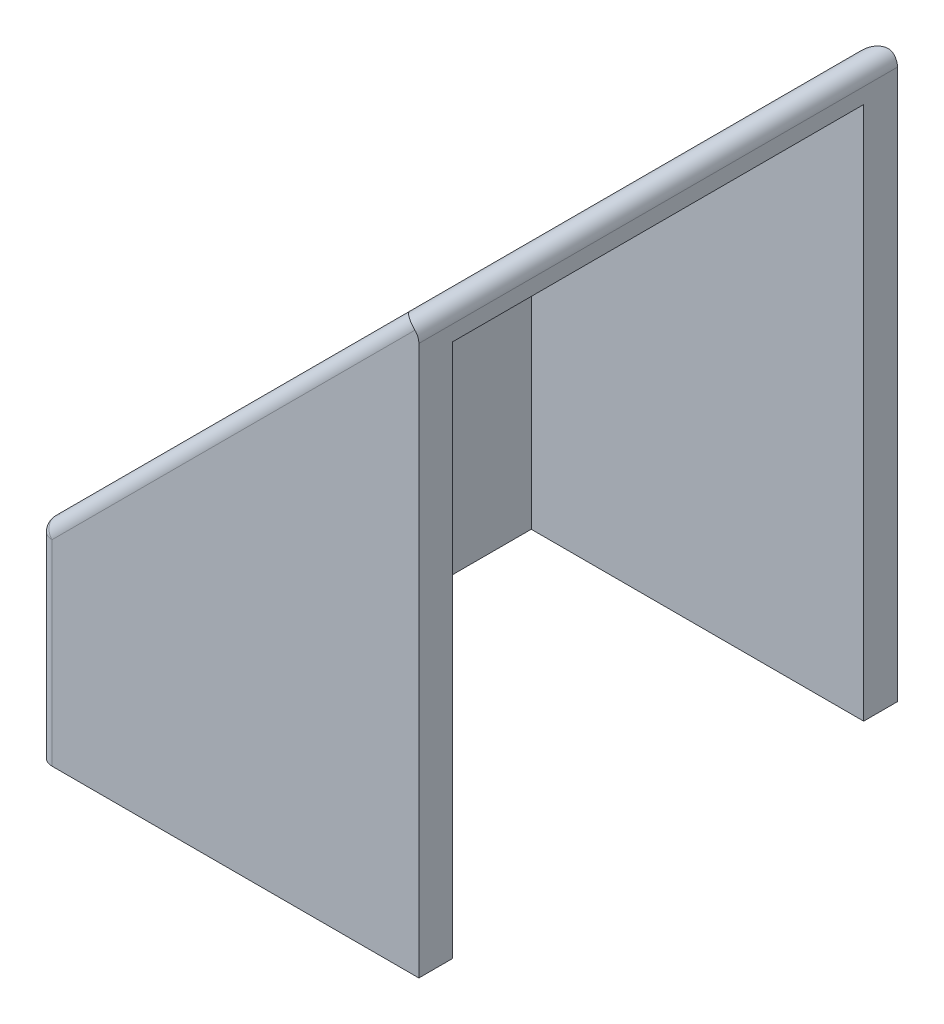
SolidWorks part; units mm, degrees
ref_plane "Front Plane" through (0, 0, 0) normal (0, 0, 1) x (1, 0, 0)
ref_plane "Top Plane" through (0, 0, 0) normal (0, 1, 0) x (1, 0, 0)
ref_plane "Right Plane" through (0, 0, 0) normal (1, 0, 0) x (0, 0, -1)
sketch "Sketch1" plane through (0, 0, 0) normal (0, 0, 1) x (1, 0, 0)
  line L0 (0, 0) -> (17.9605, 17.9605)
  line L1 (17.9605, 17.9605) -> (17.9605, 0)
  line L2 (17.9605, 0) -> (0, 0)
  dimension "D1" = 25.4
  dimension "D2" = 45
extrude "Boss-Extrude1" add sketch "Sketch1" along normal blind 22.606
sketch "Sketch2" plane through (17.9605, 0, 0) normal (1, 0, 0) x (0, 0, -1)
  line L7 (-21.006, 0) -> (-1.6, 0)
  line L10 (-1.6, 0) -> (-1.6, 16.3605)
  line L11 (-21.006, 16.3605) -> (-21.006, 0)
  line L12 (-1.6, 16.3605) -> (-21.006, 16.3605)
  line L13 (-1.6, 0) -> (-1.6, 16.3605)
  line L14 (-21.006, 16.3605) -> (-21.006, 0)
  line L15 (-1.6, 16.3605) -> (-21.006, 16.3605)
  dimension "D1" = 1.6
extrude "Cut-Extrude1" cut sketch "Sketch2" against normal offset from surface (15.6978 mm away) 1.6 up to face at (8.9803, 8.9803, 11.303)
sketch "Sketch3" plane through (0, 0, 0) normal (0, -1, 0) x (1, 0, 0)
  line L0 (17.9605, 22.606) -> (0, 22.606)
  line L1 (0, 22.606) -> (0, 0)
  line L2 (0, 0) -> (17.9605, 0)
  line L3 (17.9605, 0) -> (17.9605, 1.6)
  line L4 (17.9605, 1.6) -> (2.2627, 1.6)
  line L5 (2.2627, 1.6) -> (2.2627, 21.006)
  line L6 (2.2627, 21.006) -> (17.9605, 21.006)
  line L7 (17.9605, 21.006) -> (17.9605, 22.606)
extrude "Boss-Extrude2" add sketch "Sketch3" along normal blind 9.525
fillet "Fillet1" radius 0.635 6 edges at (17.9605, 17.9605, 11.303) (0, 0, 11.303) (8.9803, 8.9803, 0) (8.9803, 8.9803, 22.606) (0, -4.7625, 0) (0, -4.7625, 22.606)
